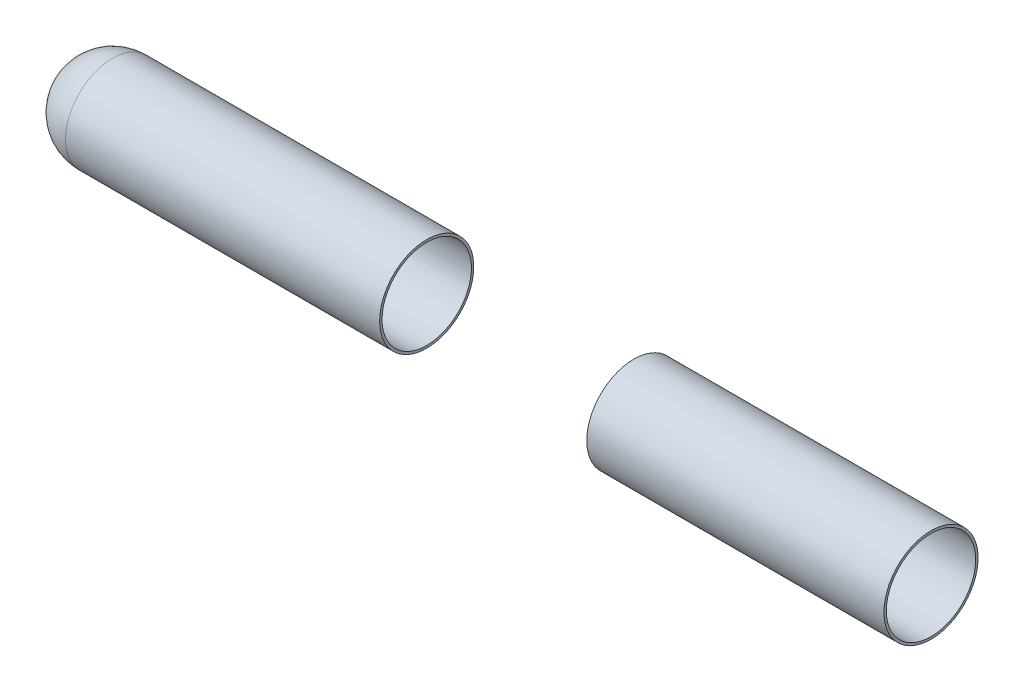
SolidWorks part; units mm, degrees
material "6063-T6"
ref_plane "Front Plane" through (0, 0, 0) normal (0, 0, 1) x (1, 0, 0)
ref_plane "Top Plane" through (0, 0, 0) normal (0, 1, 0) x (1, 0, 0)
ref_plane "Right Plane" through (0, 0, 0) normal (1, 0, 0) x (0, 0, -1)
sketch "rootSketch" plane through (0, 0, 0) normal (0, 1, 0) x (1, 0, 0)
  line L0 (0, 0) -> (12000, 0) construction
  line L1 (31.75, -31.75) -> (31.75, 31.75) construction
  line L2 (0, 0) -> (660, 0) construction
  line L3 (31.75, -31.75) -> (660, -31.75)
  line L4 (660, -31.75) -> (660, 0) construction
  line L5 (660, -31.75) -> (660, -30.1498)
  line L6 (660, -30.1498) -> (31.75, -30.1498) construction
  line L7 (1.6002, 0) -> (0, 0)
  line L8 (1.6002, 0) -> (660, 0)
  line L9 (660, 0) -> (660, -30.1498)
  arc A1 (31.75, -31.75) -> (0, 0) centre (31.75, 0) cw
  arc A2 (31.75, -30.1498) -> (1.6002, 0) centre (31.75, 0) cw construction
  point P5 (31.75, 0)
  dimension "rootMaxThickness" = 63.5
  dimension "D1" = 660
  dimension "D2" = 1.6002
revolve "Revolve1" add sketch "rootSketch" angle 360 about L0
ref_plane "Plane1" through (5330, 0, 0) normal (1, 0, 0) x (0, 0, -1)
sketch "Sketch1" plane through (0, 0, 0) normal (0, 1, 0) x (1, 0, 0)
  line L0 (660, 0) -> (660, -30.1498) construction
  line L1 (1.6002, 0) -> (660, 0) construction
  line L2 (660, -30.1498) -> (31.75, -30.1498) construction
  line L3 (660, 0) -> (660, -30.1498)
  line L4 (1.6002, 0) -> (660, 0)
  line L5 (660, -30.1498) -> (31.75, -30.1498)
  arc A0 (1.6002, 0) -> (31.75, -30.1498) centre (31.75, 0) ccw construction
  arc A1 (1.6002, 0) -> (31.75, -30.1498) centre (31.75, 0) ccw
revolve "Cut-Revolve1" cut sketch "Sketch1" angle 360 about L4
sketch "Sketch2" plane through (0, 0, 0) normal (0, 1, 0) x (1, 0, 0)
  line L0 (660, 31.75) -> (31.75, 31.75) construction
  line L1 (660, -31.75) -> (583.8, -31.75)
  line L2 (660, -31.75) -> (660, 31.75)
  line L3 (660, 31.75) -> (583.8, 31.75)
  line L4 (583.8, -31.75) -> (583.8, 31.75)
  line L5 (31.75, -31.75) -> (660, -31.75) construction
  line L6 (243.65, -31.75) -> (383.35, -31.75)
  line L7 (243.65, -31.75) -> (243.65, 31.75)
  line L8 (243.65, 31.75) -> (383.35, 31.75)
  line L9 (383.35, -31.75) -> (383.35, 31.75)
  dimension "D1" = 139.7
  dimension "D2" = 76.2
  dimension "D3" = 243.65
extrude "Cut-Extrude1" cut sketch "Sketch2" against normal through all both and the other way through all
equation "\"length\"= 0.66"
equation "\"D1@rootSketch\" = \"length\""
equation "\"diameter\"= 0.0635"
equation "\"rootMaxThickness@rootSketch\"=\"diameter\""
